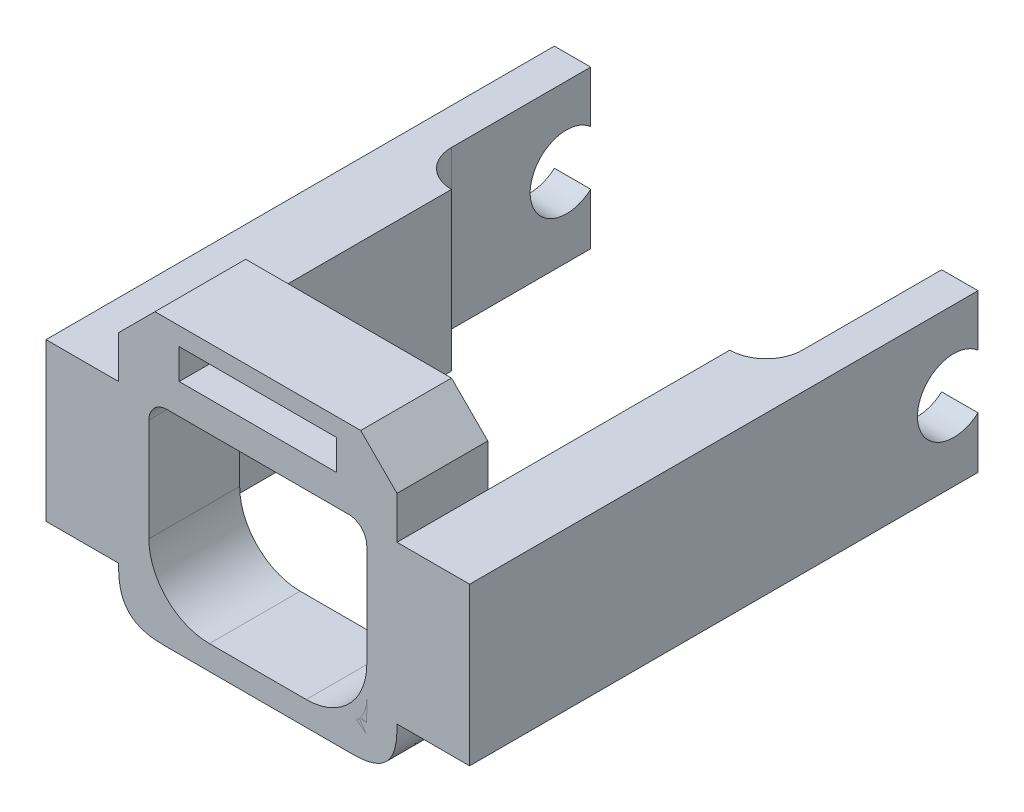
SolidWorks part; units mm, degrees
ref_plane "Front Plane" through (0, 0, 0) normal (0, 0, 1) x (1, 0, 0)
ref_plane "Top Plane" through (0, 0, 0) normal (0, 1, 0) x (1, 0, 0)
ref_plane "Right Plane" through (0, 0, 0) normal (1, 0, 0) x (0, 0, -1)
sketch "Sketch1" plane through (0, 0, 0) normal (0, 0, 1) x (1, 0, 0)
  line L0 (-18, 0) -> (0, 0)
  line L1 (0, 0) -> (0, -15)
  line L2 (0, -15) -> (-18, -15)
  line L3 (-18, -15) -> (-18, 0)
  line L4 (-20.5, 6.5) -> (-20.5, -17)
  line L5 (-20.5, -17) -> (2.5, -17)
  line L6 (2.5, -17) -> (2.5, 6.5)
  line L7 (-20.5, 6.5) -> (2.5, 6.5)
  dimension "D1" = 18
  dimension "D2" = 15
  dimension "D3" = 6.5
  dimension "D4" = 23.5
  dimension "D5" = 23
  dimension "D6" = 2.5
extrude "Boss-Extrude1" add sketch "Sketch1" along normal blind 7.5
fillet "Fillet1" radius 4 2 edges at (-20.5, -17, 3.75) (2.5, -17, 3.75) curvature continuous yes
ref_plane "Plane1" through (-18, -15, 7.5) normal (0, -1, 0) x (-1, 0, 0)
sketch "Sketch3" plane through (0, 0, 7.5) normal (0, 0, 1) x (1, 0, 0)
  line L1 (0, 0) -> (-10, -15)
  line L2 (-19.65, -15) -> (-16.35, -15) construction
  line L3 (-18, 0) -> (-18, -1.5)
  line L4 (-18, 0) -> (-18, -15) construction
  line L5 (-18, 0) -> (-16.5, 0)
  arc A0 (-18, -1.5) -> (-16.5, 0) centre (-16.5, -1.5) cw
  line M13 (-18, -15) -> (-18, 0)
  line M14 (-18, 0) -> (0, 0)
extrude "Boss-Extrude2" add sketch "Sketch3" against normal blind 7.5 contours A0 M13 M14 region at (-17.6649, -0.3351, 7.5)
sketch "Sketch4" plane through (0, 0, 7.5) normal (0, 0, 1) x (1, 0, 0)
  line L0 (0, 0) -> (0, -1.4954)
  line L1 (0, -15) -> (0, 0) construction
  line L2 (0, 0) -> (-1.4954, 0)
  line L3 (0, 0) -> (-16.5, 0) construction
  arc A0 (0, -1.4954) -> (-1.4954, 0) centre (-1.4954, -1.4954) ccw
extrude "Boss-Extrude3" add sketch "Sketch4" against normal blind 7.5
sketch "Sketch6" plane through (0, 0, 7.5) normal (0, 0, 1) x (1, 0, 0)
  line L0 (0, -15) -> (0, -12.5)
  line L1 (0, -15) -> (0, -1.4954) construction
  line L2 (0, -15) -> (-2.5, -15)
  line L3 (-18, -15) -> (0, -15) construction
  arc A0 (-2.5, -15) -> (0, -12.5) centre (-2.5, -12.5) ccw
extrude "Boss-Extrude4" add sketch "Sketch6" against normal blind 7.5 separate body
sketch "Sketch7" plane through (0, 0, 7.5) normal (0, 0, 1) x (1, 0, 0)
  line L0 (-18, -15) -> (-13, -15)
  line L1 (-19.65, -15) -> (-16.35, -15) construction
  line L2 (-18, -1.5) -> (-18, -15) construction
  line L3 (-18, -15) -> (-18, -10)
  line L4 (0, -15) -> (-5, -15)
  line L5 (-18, -15) -> (0, -15) construction
  line L6 (0, -15) -> (0, -10)
  line L7 (0, -15) -> (0, -1.4954) construction
  arc A0 (-13, -15) -> (-18, -10) centre (-13, -10) cw
  arc A1 (-5, -15) -> (0, -10) centre (-5, -10) ccw
extrude "Boss-Extrude11" add sketch "Sketch7" against normal blind 7.5
chamfer "Chamfer1" distance 3 angle 45 2 edges at (2.5, 6.5, 3.75) (-20.5, 6.5, 3.75)
sketch "Sketch8" plane through (0, 0, 7.5) normal (0, 0, 1) x (1, 0, 0)
  line L0 (-15.5, 5) -> (-2.5, 5)
  line L1 (-2.5, 5) -> (-2.5, 2.5)
  line L2 (-2.5, 2.5) -> (-15.5, 2.5)
  line L3 (-15.5, 2.5) -> (-15.5, 5)
  line L4 (-5.8308, -17) -> (-5.8308, -11.5283)
  line L5 (-16.5, -17) -> (-1.5, -17) construction
  line L6 (-5.8308, -11.5283) -> (-4.4006, -11.5283)
  line L7 (-4.4006, -11.5283) -> (-4.4006, -17)
  line L8 (-20.5, 3.5) -> (-20.5, -13) construction
  line L10 (-1.4954, 0) -> (-16.5, 0) construction
  dimension "D1" = 5
  dimension "D2" = 2.5
  dimension "D3" = 2.5
extrude "Cut-Extrude1" cut sketch "Sketch8" against normal blind 7.5 contours L3 L2 L1 L0 region at (-9, 3.75, 7.5)
ref_plane "Plane3" through (-9, 0, 0) normal (-1, 0, 0) x (0, 0, 1)
sketch "Sketch9" plane through (0, 0, 0) normal (0, 0, -1) x (-1, 0, 0)
  line L0 (20.5, 0) -> (26.5, 0)
  line L1 (20.5, 3.5) -> (20.5, -13) construction
  line L5 (26.5, 0) -> (26.5, -13)
  line L6 (26.5, -13) -> (20.5, -13)
  line L7 (20.5, -13) -> (20.5, 0)
extrude "Boss-Extrude12" add sketch "Sketch9" along normal blind 45 and the other way blind 7.5
sketch "Sketch10" plane through (0, 0, 0) normal (0, 1, 0) x (1, 0, 0)
  line L0 (-23.5, 45) -> (-23.5, 20)
  line L1 (-26.5, 45) -> (-20.5, 45) construction
  line L2 (-23.5, 20) -> (-20.5, 20)
  line L3 (-20.5, 0) -> (-20.5, 45) construction
sketch "Sketch11" plane through (0, 0, -45) normal (0, 0, -1) x (-1, 0, 0)
  line L0 (23.5, 0) -> (23.5, -13)
  line L1 (23.5, 0) -> (20.5, 0) construction
  line L2 (20.5, -13) -> (26.5, -13) construction
  line L3 (23.5, -13) -> (20.5, -13)
  line L4 (20.5, -13) -> (20.5, 0)
  line L5 (20.5, 0) -> (20.5, -13) construction
  line L6 (20.5, 0) -> (23.5, 0)
extrude "Cut-Extrude3" cut sketch "Sketch11" against normal blind 25
fillet "Fillet3" radius 3 1 edges at (-23.5, -6.5, -20)
mirror "Mirror7" about plane through (-9, 0, 0) normal (-1, 0, 0) of "Cut-Extrude3", "Fillet3", "Boss-Extrude12"
sketch "Sketch12" plane through (-26.5, 0, 0) normal (-1, 0, 0) x (0, 0, 1)
  line L0 (7.5, -6.5) -> (-32.5, -6.5)
  line L1 (7.5, -13) -> (7.5, 0) construction
  line L2 (-45, 0) -> (-34.5, 0)
  line L3 (-45, 0) -> (-20, 0) construction
  line L4 (-34.5, 0) -> (-34.5, -13)
  line L5 (7.5, -13) -> (-45, -13) construction
  line L6 (-34.5, -13) -> (-45, -13)
  line L7 (-45, -13) -> (-45, 0)
  circle A0 centre (-32.5, -6.5) radius 3
  line M2 (7.5, 0) -> (-45, 0)
  line M3 (-45, 0) -> (-45, -13)
  line M4 (-45, -13) -> (7.5, -13)
extrude "Cut-Extrude4" cut sketch "Sketch12" against normal through all contours A0 L4 | L4 A0 | A0 L4 M2 M3 M4 | A0 region at (-26.5, -6.5, -39.8625) region at (-26.5, -3.8327, -31.3071) region at (-26.5, -6.5, -34.9063)
